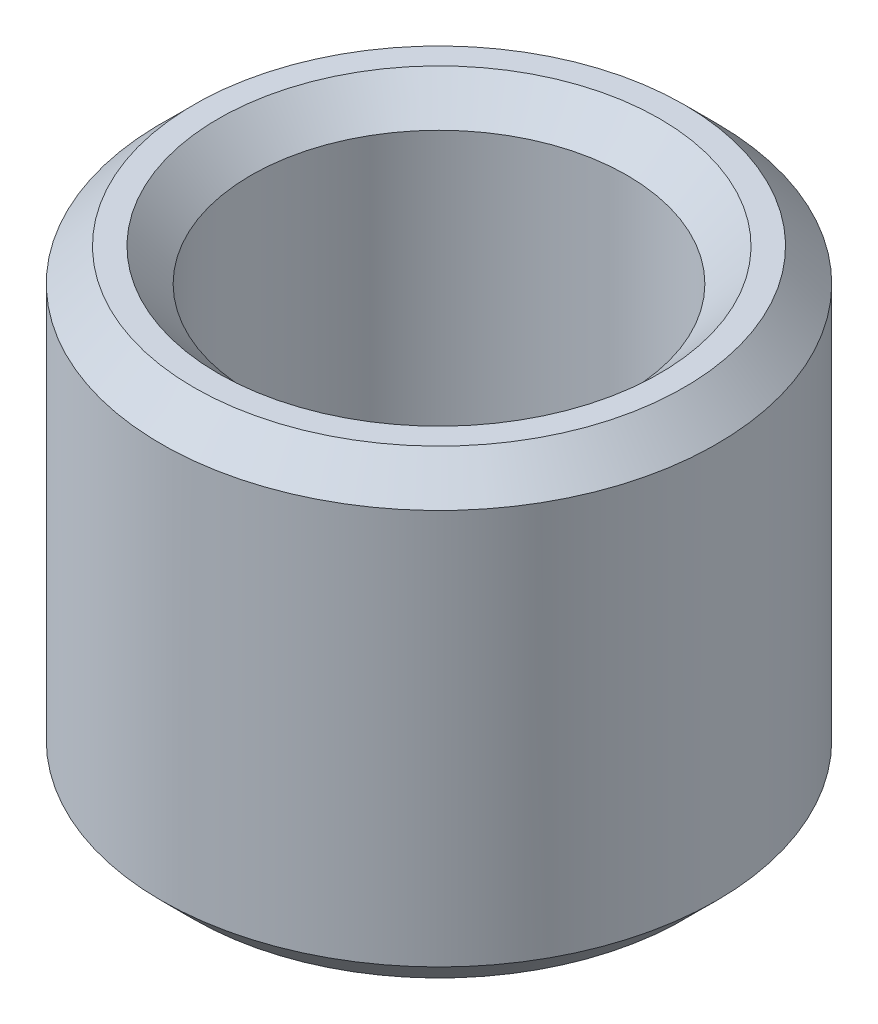
SolidWorks part; units mm, degrees
ref_plane "Front Plane" through (0, 0, 0) normal (0, 0, 1) x (1, 0, 0)
ref_plane "Top Plane" through (0, 0, 0) normal (0, 1, 0) x (1, 0, 0)
ref_plane "Right Plane" through (0, 0, 0) normal (1, 0, 0) x (0, 0, -1)
sketch "Sketch1" plane through (0, 0, 0) normal (0, 1, 0) x (1, 0, 0)
  circle A0 centre (0, 0) radius 7.5
  dimension "SLEEVE_OD" = 15
extrude "Boss-Extrude1" add sketch "Sketch1" along normal blind 12.4398
sketch "Sketch2" plane through (0, 0, 0) normal (0, 1, 0) x (1, 0, 0)
  circle A0 centre (0, 0) radius 5.0777
  dimension "BORE_D" = 10.1555
extrude "Cut-Extrude1" cut sketch "Sketch2" along normal through all
chamfer "Chamfer1" distance 0.8818 angle 45 4 edges at (0, 12.4398, 5.0777) (0, 0, 5.0777) (0, 0, 7.5) (0, 12.4398, 7.5)
